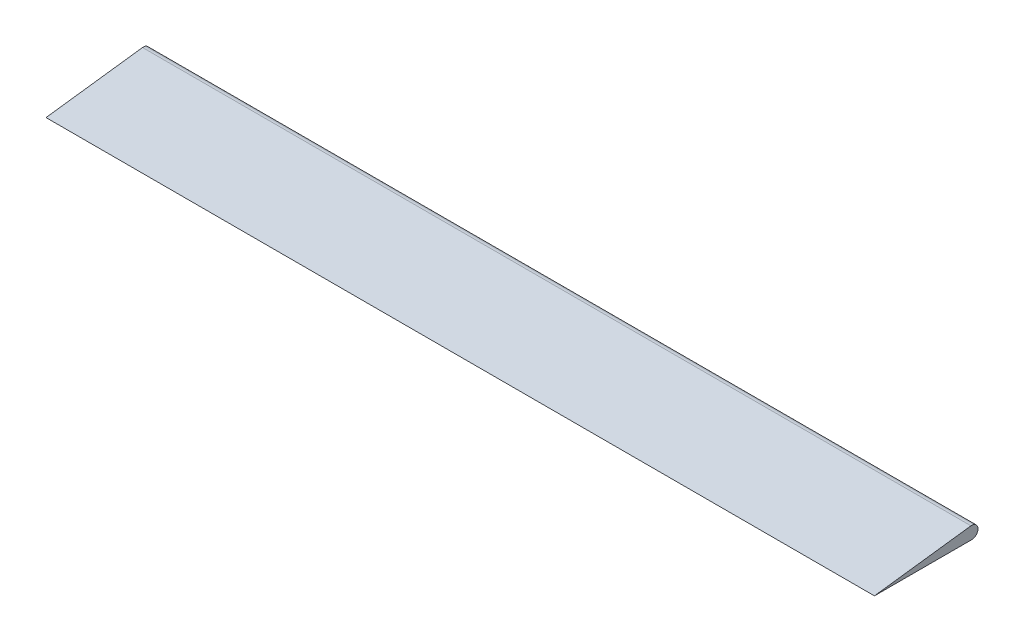
SolidWorks part; units mm, degrees
ref_plane "Front Plane" through (0, 0, 0) normal (0, 0, 1) x (1, 0, 0)
ref_plane "Top Plane" through (0, 0, 0) normal (0, 1, 0) x (1, 0, 0)
ref_plane "Right Plane" through (0, 0, 0) normal (1, 0, 0) x (0, 0, -1)
sketch "Sketch1" plane through (0, 0, 0) normal (1, 0, 0) x (0, 0, -1)
  line L0 (0, 0) -> (234.9384, 0)
  line L1 (0, 0) -> (233.0151, 30)
  line L2 (250, 814.8547) -> (250, -450.4019) construction
  arc A0 (233.0151, 30) -> (234.9384, 0) centre (234.9384, 15.0616) cw
  dimension "D1" = 250
  dimension "D2" = 30
extrude "Boss-Extrude1" add sketch "Sketch1" along normal blind 2000
